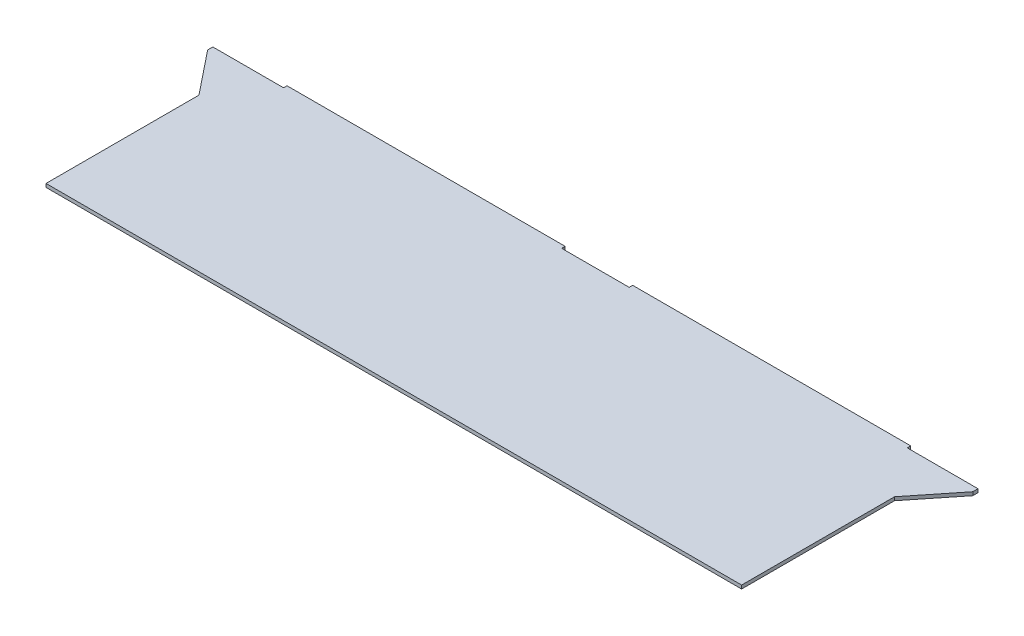
SolidWorks part; units mm, degrees
material "6061-T6 (SS)"
ref_plane "X-Y Datum" through (0, 0, 0) normal (0, 0, 1) x (1, 0, 0)
ref_plane "X-Z Datum" through (0, 0, 0) normal (0, 1, 0) x (1, 0, 0)
ref_plane "Y-Z Datum" through (0, 0, 0) normal (1, 0, 0) x (0, 0, -1)
sketch "Sketch1" plane through (0, 0, 0) normal (0, 1, 0) x (1, 0, 0)
  line L1 (-317.6778, 92.075) -> (317.6778, 92.075)
  line L2 (-317.6778, 92.075) -> (-317.6778, -92.075)
  line L3 (-317.6778, -92.075) -> (317.6778, -92.075)
  line L4 (317.6778, 92.075) -> (317.6778, -92.075)
  line L5 (-317.6778, 92.075) -> (317.6778, -92.075) construction
  line L6 (-317.6778, -92.075) -> (317.6778, 92.075) construction
  point P0 (0, 0)
  dimension "D1" = 635.3556
  dimension "D2" = 184.15
extrude "Boss-Extrude1" add sketch "Sketch1" along normal mid plane 3.175
sketch "Sketch2" plane through (0, 0, -92.075) normal (0, 0, -1) x (-1, 0, 0)
  line L20 (-317.6778, -1.5875) -> (317.6778, -1.5875) construction
  line L21 (-284.8229, -1.5875) -> (-30.8229, -1.5875)
  line L22 (30.8229, -1.5875) -> (284.8229, -1.5875)
  line L40 (30.8229, -1.5875) -> (30.8229, 1.5875)
  line L41 (30.8229, 1.5875) -> (284.8229, 1.5875)
  line L42 (284.8229, 1.5875) -> (284.8229, -1.5875)
  line L56 (-284.8229, -1.5875) -> (-284.8229, 1.5875)
  line L57 (-284.8229, 1.5875) -> (-30.8229, 1.5875)
  line L58 (-30.8229, 1.5875) -> (-30.8229, -1.5875)
extrude "Boss-Extrude2" add sketch "Sketch2" along normal blind 3.175
sketch "Sketch3" plane through (0, -1.5875, 0) normal (0, -1, 0) x (1, 0, 0)
  line L0 (317.6778, -92.075) -> (349.4278, -92.075)
  line L1 (349.4278, -92.075) -> (349.4278, -87.3125)
  line L3 (349.4278, -87.3125) -> (317.6778, -47.625)
  line L4 (317.6778, 92.075) -> (317.6778, -92.075) construction
  line L17 (317.6778, -92.075) -> (317.6778, 92.075)
  line L18 (317.6778, 92.075) -> (-317.6778, 92.075)
  line L19 (-317.6778, 92.075) -> (-317.6778, -92.075)
  line L20 (-317.6778, -92.075) -> (-284.8229, -92.075)
  line L21 (-284.8229, -92.075) -> (-284.8229, -95.25)
  line L22 (-284.8229, -95.25) -> (-30.8229, -95.25)
  line L23 (-30.8229, -95.25) -> (-30.8229, -92.075)
  line L24 (-30.8229, -92.075) -> (30.8229, -92.075)
  line L25 (30.8229, -92.075) -> (30.8229, -95.25)
  line L26 (30.8229, -95.25) -> (284.8229, -95.25)
  line L27 (284.8229, -95.25) -> (284.8229, -92.075)
  line L28 (284.8229, -92.075) -> (317.6778, -92.075)
  line L29 (317.6778, -92.075) -> (317.6778, -47.625)
  point P11 (0, 0)
  dimension "D1" = 31.75
  dimension "D2" = 4.7625
  dimension "D3" = 44.45
  dimension "D4" = 0
extrude "Boss-Extrude3" add sketch "Sketch3" against normal blind 3.175
mirror "Mirror1" about plane through (0, 0, 0) normal (1, 0, 0) of "Boss-Extrude3"
